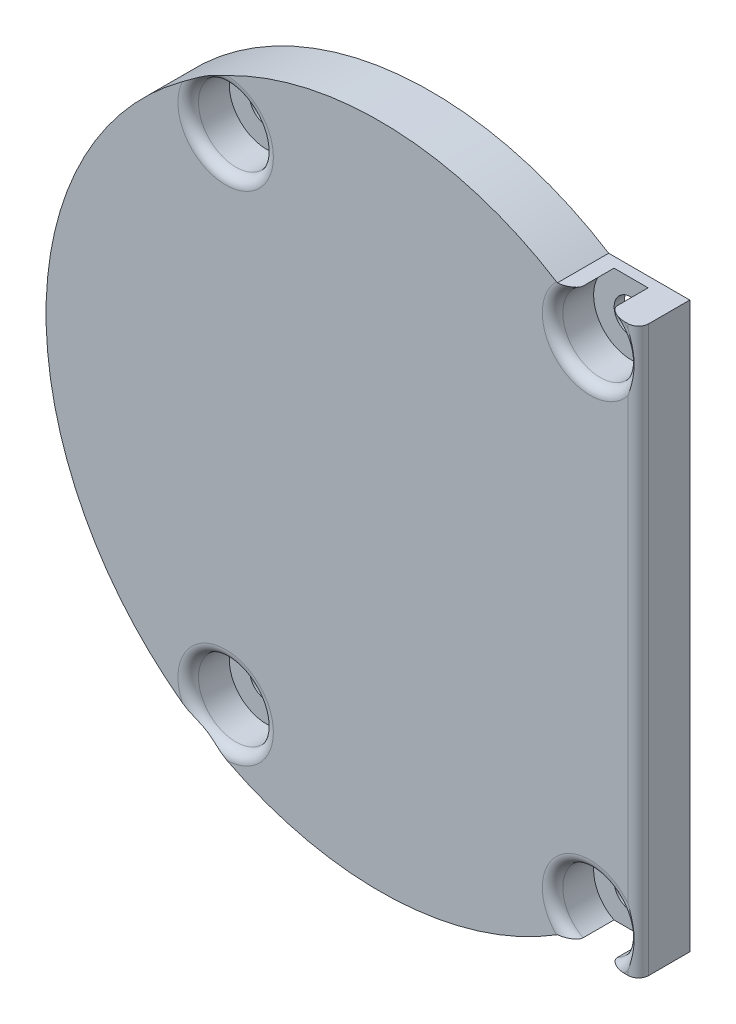
SolidWorks part; units mm, degrees
ref_plane "Ebene vorne" through (0, 0, 0) normal (0, 0, 1) x (1, 0, 0)
ref_plane "Ebene oben" through (0, 0, 0) normal (0, 1, 0) x (1, 0, 0)
ref_plane "Ebene rechts" through (0, 0, 0) normal (1, 0, 0) x (0, 0, -1)
sketch "Skizze1" plane through (0, 0, 0) normal (0, 0, 1) x (1, 0, 0)
  line L0 (30.5, 21) -> (30.5, -21)
  line L1 (15, -24.25) -> (-15, -24.25)
  line L2 (15, -24.25) -> (15, 24.25)
  line L3 (15, 24.25) -> (-15, 24.25)
  line L4 (-15, -24.25) -> (-15, 24.25)
  line L5 (15, -24.25) -> (-15, 24.25) construction
  line L6 (15, 24.25) -> (-15, -24.25) construction
  line L7 (30.5, -27.5) -> (30.5, 27.5)
  line L8 (30.5, 27.5) -> (30.5, 21)
  line L9 (30.5, 24.25) -> (26.2718, 24.25) construction
  line L10 (30.5, 27.5) -> (17.3205, 27.5)
  line L11 (30.5, 21) -> (24.8042, 21)
  line L12 (0, 0) -> (8.2887, 0) construction
  line L13 (30.5, 27.5) -> (25.22, 27.5)
  line L14 (30.5, 27.5) -> (30.5, -27.5)
  line L15 (30.5, -27.5) -> (25.22, -27.5)
  line L16 (25.22, 27.5) -> (25.22, -27.5)
  line L17 (30.5, 27.5) -> (25.22, -27.5) construction
  line L18 (30.5, -27.5) -> (25.22, 27.5) construction
  line L19 (25.22, -27.5) -> (17.3205, -27.5)
  circle A0 centre (0, 0) radius 32.5
  circle A1 centre (-15, 24.25) radius 1.65
  circle A2 centre (20.5, 24.25) radius 1.65
  circle A3 centre (20.5, -24.25) radius 1.65
  circle A4 centre (-15, -24.25) radius 1.65
  point P10 (30.5, 0)
  point P16 (30.5, 0)
  point P22 (27.86, 0)
  dimension "D1" = 65
  dimension "D5" = 3.3
  dimension "D7" = 3.3
  dimension "D2" = 30
  dimension "D3" = 30.5
  dimension "D4" = 42
  dimension "D6" = 10
  dimension "D8" = 55
  dimension "D9" = 5.28
extrude "Aufsatz-Linear austragen1" add sketch "Skizze1" along normal blind 5 contours A0 A3 L16 A2 L1 A4 L4 A1 L3 L2 | L4 A4 L1 L2 L3 A1 | A0 A3 L19 L16 | A2 A0 L11 L16 L10 | A0 L16 L11 region at (25.0819, 20.8335, 0) region at (22.8546, 25.3317, 0) region at (24.3507, 0, 0) region at (22.8648, -25.3111, 0) region at (0.0422, 0, 0)
sketch "Skizze2" plane through (0, 0, 5) normal (0, 0, 1) x (1, 0, 0)
  line L0 (0, 0) -> (4.0673, 0) construction
  circle A0 centre (-15, 24.25) radius 3.65
  circle A1 centre (20.5, 24.25) radius 3.65
  circle A2 centre (20.5, -24.25) radius 3.65
  circle A3 centre (-15, -24.25) radius 3.65
  dimension "D1" = 7.3
  dimension "D2" = 7.3
extrude "Schnitt-Linear austragen1" cut sketch "Skizze2" against normal blind 4
fillet "Verrundung10" radius 1 5 edges at (20.5, 20.6, 5) (25.22, 0, 5) (20.5, -20.6, 5) (-18.65, -24.25, 5) (-11.35, 24.25, 5)
